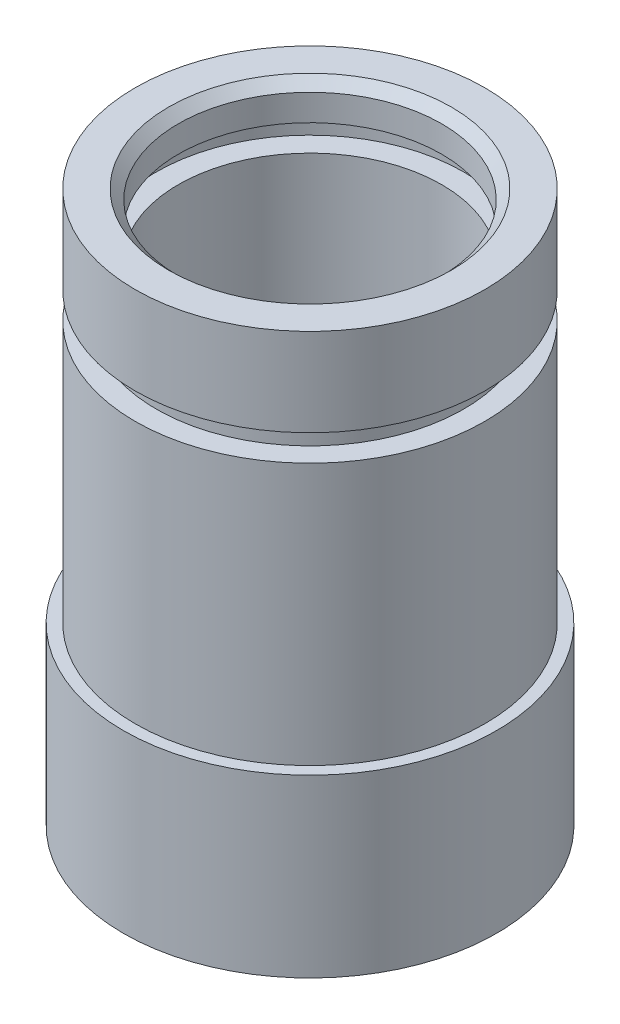
SolidWorks part; units mm, degrees
material "6061 Alloy"
ref_plane "Front Plane" through (0, 0, 0) normal (0, 0, 1) x (1, 0, 0)
ref_plane "Top Plane" through (0, 0, 0) normal (0, 1, 0) x (1, 0, 0)
ref_plane "Right Plane" through (0, 0, 0) normal (1, 0, 0) x (0, 0, -1)
sketch "Sketch1" plane through (0, 0, 0) normal (0, 0, 1) x (1, 0, 0)
  line L0 (0, 0) -> (0, 10.9165) construction
  line L1 (19.05, -37.5473) -> (19.05, 4.1087)
  line L2 (19.05, 4.1087) -> (20.447, 5.5057)
  line L3 (20.447, 5.5057) -> (25.2857, 5.5057)
  line L6 (25.2857, 5.5057) -> (25.2857, -37.5473)
  line L7 (25.2857, -37.5473) -> (19.05, -37.5473)
  line L8 (19.05, -37.5473) -> (15.875, -37.5473)
  line L9 (15.875, -37.5473) -> (25.7175, -74.28)
  line L11 (25.7175, -74.28) -> (26.9875, -74.28)
  line L13 (15.875, -37.5473) -> (7.9375, -7.9242) construction
  line L14 (26.9875, -48.88) -> (26.9875, -74.28)
  line L15 (25.2857, -37.5473) -> (25.2857, -48.88)
  line L16 (-26.9875, -48.88) -> (26.9875, -48.88) construction
  line L17 (25.2857, -48.88) -> (26.9875, -48.88)
  line L18 (-26.9875, -48.88) -> (-26.9875, -74.28)
  line L19 (-26.9875, -74.28) -> (26.9875, -74.28) construction
  line L20 (-22.2123, 5.5057) -> (22.2123, 5.5057) construction
  line L21 (19.05, 0.2987) -> (22.225, 0.2987)
  line L22 (25.2857, -7.1943) -> (22.225, -7.1943)
  line L23 (25.2857, -7.1943) -> (25.2857, -11.0043)
  line L24 (25.2857, -11.0043) -> (22.225, -11.0043)
  line L25 (22.225, -7.1943) -> (22.225, -11.0043)
  line L26 (19.05, 0.2987) -> (19.05, -3.5113)
  line L27 (19.05, -3.5113) -> (22.225, -3.5113)
  line L28 (22.225, 0.2987) -> (22.225, -3.5113)
  line L29 (-25.7175, -74.28) -> (-26.9875, -74.28)
  line L30 (-15.875, -37.5473) -> (-25.7175, -74.28)
  line L31 (-22.225, 0.2987) -> (-22.225, -3.5113)
  line L32 (-19.05, -3.5113) -> (-22.225, -3.5113)
  line L33 (-19.05, 0.2987) -> (-19.05, -3.5113)
  line L34 (-22.225, -7.1943) -> (-22.225, -11.0043)
  line L35 (-25.2857, -11.0043) -> (-22.225, -11.0043)
  line L36 (-25.2857, -7.1943) -> (-25.2857, -11.0043)
  line L37 (-25.2857, -7.1943) -> (-22.225, -7.1943)
  line L38 (-19.05, 0.2987) -> (-22.225, 0.2987)
  line L39 (-25.2857, -48.88) -> (-26.9875, -48.88)
  line L40 (-25.2857, -37.5473) -> (-25.2857, -48.88)
  line L41 (-19.05, -37.5473) -> (-15.875, -37.5473)
  line L42 (-25.2857, -37.5473) -> (-19.05, -37.5473)
  line L43 (-25.2857, 5.5057) -> (-25.2857, -37.5473)
  line L44 (-20.447, 5.5057) -> (-25.2857, 5.5057)
  line L45 (-19.05, 4.1087) -> (-20.447, 5.5057)
  line L46 (-19.05, -37.5473) -> (-19.05, 4.1087)
  point P26 (25.2857, 5.5057)
  point P37 (15.875, -37.5473)
  point P53 (-15.875, -37.5473)
  point P54 (-25.2857, 5.5057)
  dimension "D1" = 44.45
  dimension "D2" = 12.7
  dimension "D3" = 44.45
  dimension "D4" = 3.81
  dimension "D5" = 19.05
  dimension "D6" = 45
  dimension "D7" = 1.397
  dimension "D8" = 3.0607
  dimension "D9" = 3.81
revolve "Revolve1" add sketch "Sketch1" angle 360 about L0 region at (22.1785, -17.1517, 0) region at (22.9715, -51.7733, 0)
